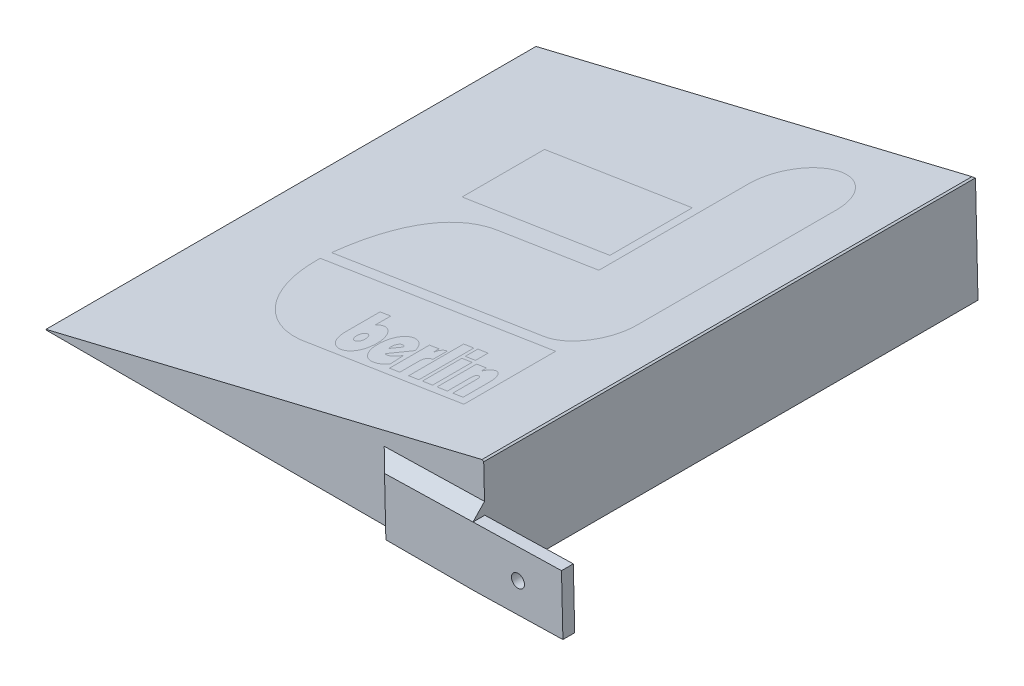
SolidWorks part; units mm, degrees
note: The reader was unsure of these and kept them because the rebuilt part matched: shared geometry of "Sketch14<4>".
ref_plane "Front Plane" through (0, 0, 0) normal (0, 0, 1) x (1, 0, 0)
ref_plane "Top Plane" through (0, 0, 0) normal (0, 1, 0) x (1, 0, 0)
ref_plane "Right Plane" through (0, 0, 0) normal (1, 0, 0) x (0, 0, -1)
sketch "Sketch1" plane through (0, 0, 0) normal (0, 0, 1) x (1, 0, 0)
  line L0 (0, 0) -> (-499.8557, 0) construction
  line L1 (0, 0) -> (50, 0)
  line L2 (0, 0) -> (0, 48)
  line L3 (0, 48) -> (50, 48)
  line L4 (50, 0) -> (50, 48)
  line L5 (-499.8557, 0) -> (-500.7205, 35.9896)
  line L6 (-500.7205, 35.9896) -> (-0.8647, 48)
  line L7 (-499.8557, 0) -> (0, 12.0104)
  line L8 (0, 12.0104) -> (-0.8647, 48)
  line L9 (-500.3361, 19.9942) -> (-0.4804, 32.0046)
  line L10 (0, 32) -> (50, 32)
  line L11 (0, 12) -> (50, 12)
  point P13 (0, 0)
  point P14 (0, 0)
  dimension "D1" = 48
  dimension "D2" = 50
  dimension "D3" = 36
  dimension "D4" = 500
  dimension "D5" = 20
  dimension "D6" = 32
  dimension "D7" = 12
sketch "Sketch2" plane through (0, 0, 0) normal (0, 0, 1) x (1, 0, 0)
  line L0 (0, 12) -> (-40, 11.0493)
  line L1 (-499.8557, 0) -> (0, 12.0104) construction
  line L2 (-40, 11.0493) -> (-40, 0)
  line L3 (0, 0) -> (-499.8557, 0) construction
  line L4 (-40, 0) -> (0, 0)
  line L5 (0, 0) -> (0, 12)
  dimension "D1" = 40
sketch "Sketch3" plane through (0, 0, 0) normal (0, 0, 1) x (1, 0, 0)
  line L0 (-39.9885, 11.0496) -> (-40.4689, 31.0438)
  line L1 (-499.8557, 0) -> (0, 12.0104) construction
  line L2 (-500.3361, 19.9942) -> (-0.4804, 32.0046) construction
  line L3 (-40.4689, 31.0438) -> (-0.4804, 32.0046)
  line L4 (-0.4804, 32.0046) -> (39.5196, 32)
  line L5 (0, 32) -> (50, 32) construction
  line L7 (0, 12) -> (50, 12) construction
  line L8 (39.5196, 12) -> (0, 12)
  line L9 (0, 12) -> (-39.9885, 11.0496)
  line L10 (-40.2287, 21.0467) -> (-0.2402, 22.0075) construction
  line L11 (0, 12.0104) -> (-0.8647, 48) construction
  line L12 (39.5196, 32) -> (39.5196, 12)
  line L13 (39.5196, 22) -> (0, 22) construction
  line L14 (0, 0) -> (0, 48) construction
  circle A0 centre (19.7598, 22) radius 2.2
  circle A1 centre (-20.2344, 21.5271) radius 2.2
  dimension "D3" = 4.4
  dimension "D1" = 40
  dimension "D2" = 40
sketch "Sketch4" plane through (0, 0, 0) normal (0, 0, 1) x (1, 0, 0)
  line L0 (-499.8558, 0) -> (-769.6838, 0) construction
  line L1 (-500.7205, 35.9896) -> (-649.8557, 0)
  line L2 (-649.8557, 0) -> (-499.8557, 0)
  line L3 (-499.8557, 0) -> (-500.7205, 35.9896)
  point P2 (-504.4259, 33.421)
  dimension "D1" = 150
extrude "Boss-Extrude1" add sketch "Sketch4" against normal blind 166.6667
ref_plane "Plane1" through (0, 0, -3) normal (0, 0, 1) x (1, 0, 0)
sketch "Sketch6" plane through (0, 0, -3) normal (0, 0, 1) x (1, 0, 0)
  line L0 (-504.8572, 0) -> (-505.5702, 29.6757)
  line L1 (-649.8557, 0) -> (-499.8557, 0) construction
  line L2 (-505.5702, 29.6757) -> (-585.109, 10.4813)
  line L3 (-585.109, 10.4813) -> (-584.8572, 0)
  line L4 (-584.8572, 0) -> (-504.8572, 0)
  line L5 (-499.8557, 0) -> (-500.7205, 35.9896) construction
  line L6 (-500.7205, 35.9896) -> (-649.8557, 0) construction
  point P8 (-585.8895, 4.3637)
  dimension "D1" = 5
  dimension "D2" = 5
  dimension "D3" = 80
extrude "Cut-Extrude1" cut sketch "Sketch6" against normal offset from surface (160.6667 mm away) 3 up to face at (-550.144, 11.9965, -166.6667)
sketch "Sketch7" plane through (-499.5673, -12.0035, 0) normal (0.9997, 0.024, 0) x (0, 0, -1)
  line L0 (20, 48.0069) -> (20, 12.0069) construction
  line L1 (166.6667, 48.0069) -> (0, 48.0069) construction
  line L2 (166.6667, 12.0069) -> (0, 12.0069) construction
  line L3 (0, 12.0069) -> (0, 48.0069) construction
  line L4 (20, 48.0069) -> (0, 12.0069) construction
  circle A0 centre (10, 30.0069) radius 2.75
  dimension "D2" = 5.5
  dimension "D1" = 20
extrude "Cut-Extrude2" [suppressed] cut sketch "Sketch7" against normal up to surface (5 mm away)
sketch "Sketch8" plane through (0, 0, 0) normal (0, 0, 1) x (1, 0, 0)
  line L0 (-500.3361, 19.9942) -> (-470.3448, 20.7149)
  line L1 (-500.3361, 19.9942) -> (-0.4804, 32.0046) construction
  line L2 (-470.3448, 20.7149) -> (-469.8644, 0.7206)
  line L3 (-499.8557, 0) -> (0, 12.0104) construction
  line L4 (-469.8644, 0.7206) -> (-499.8557, 0)
  line L5 (-499.8557, 0) -> (-529.8644, 0)
  line L6 (-649.8557, 0) -> (-499.8557, 0) construction
  line L7 (-529.8644, 0) -> (-530.3275, 19.2736)
  line L9 (-499.8557, 0) -> (-500.7205, 35.9896) construction
  line L10 (-500.3361, 19.9942) -> (-530.3275, 19.2736)
  point P15 (-510.374, 21.4504)
  dimension "D1" = 30
  dimension "D2" = 30
extrude "Boss-Extrude2" add sketch "Sketch8" along normal blind 4
sketch "Sketch9" plane through (0, 0, 4) normal (0, 0, 1) x (1, 0, 0)
  line L0 (-500.3361, 19.9942) -> (-469.8644, 0.7206) construction
  circle A0 centre (-485.1003, 10.3574) radius 2.2
  point P6 (-500.5629, 16.3746)
  dimension "D1" = 4.4
extrude "Cut-Extrude3" cut sketch "Sketch9" against normal through all
sketch "Sketch10" plane through (0, 0, -166.6667) normal (0, 0, -1) x (-1, 0, 0)
  line L0 (527.1478, 12) -> (513.1478, 12) construction
  line L2 (649.8557, 0) -> (499.8557, 0) construction
  line L3 (499.8557, 0) -> (500.7205, 35.9896) construction
  circle A0 centre (513.1478, 12) radius 2.2
  circle A1 centre (527.1478, 12) radius 2.2
  point P4 (524.0125, 6.3666)
  dimension "D1" = 4.4
  dimension "D2" = 12
  dimension "D3" = 14
  dimension "D4" = 13
extrude "Cut-Extrude4" cut sketch "Sketch10" against normal up to surface (3 mm away) up to face at (-545.0984, 10.0393, -163.6667)
chamfer "Chamfer3" distance 0.6 angle 45 3 edges at (-649.8557, 0, -83.3333) (-500.7205, 35.9896, -83.3333) (-575.2881, 17.9948, -166.6667)
chamfer "Chamfer4" distance 1 angle 45 1 edges at (-649.8557, 0, -83.0333)
sketch "Sketch14" plane through (-35.7625, 148.1942, 0) normal (-0.2346, 0.9721, 0) x (0.9721, 0.2346, 0)
  line L0 (-536.5022, 24.6662) -> (-532.5391, 24.2846)
  line L1 (-532.5391, 24.2846) -> (-532.5391, 30.6936)
  line L2 (-530.0307, 33.034) -> (-530.0115, 37.9765)
  line L3 (-532.7432, 35.7033) -> (-532.784, 35.7057)
  line L4 (-532.784, 35.7057) -> (-532.784, 37.8757)
  line L5 (-532.784, 37.8757) -> (-536.5022, 38.1901)
  line L6 (-536.5022, 38.1901) -> (-536.5022, 24.6662)
  line L7 (-525.1531, 23.574) -> (-525.1531, 42.1916)
  line L8 (-525.1531, 42.1916) -> (-529.0849, 42.5733)
  line L9 (-529.0849, 42.5733) -> (-529.0849, 23.9533)
  line L10 (-529.0849, 23.9533) -> (-525.1531, 23.574)
  line L11 (-519.8482, 37.6116) -> (-519.8482, 41.8579)
  line L12 (-519.8482, 41.8579) -> (-523.8088, 42.2636)
  line L13 (-523.8088, 42.2636) -> (-523.8088, 38.0125)
  line L14 (-523.8088, 38.0125) -> (-519.8482, 37.6116)
  line L15 (-519.8482, 23.0604) -> (-519.8482, 36.4594)
  line L16 (-519.8482, 36.4594) -> (-523.8088, 36.8603)
  line L17 (-523.8088, 36.8603) -> (-523.8088, 23.4636)
  line L18 (-523.8088, 23.4636) -> (-519.8482, 23.0604)
  line L19 (-561.0824, 45.3337) -> (-561.0824, 33.891)
  line L20 (-556.9681, 39.6832) -> (-556.9681, 45.0001)
  line L21 (-556.9681, 45.0001) -> (-561.0824, 45.3337)
  line L22 (-543.2761, 29.7839) -> (-537.5896, 34.4335)
  line L23 (-538.0097, 26.3753) -> (-538.3289, 31.3418)
  line L24 (-518.1271, 36.3346) -> (-518.1271, 22.9163)
  line L25 (-518.1271, 22.9163) -> (-514.0968, 22.5011)
  line L26 (-514.0968, 22.5011) -> (-514.0968, 30.4152)
  line L27 (-512.0228, 30.6576) -> (-512.0228, 22.309)
  line L28 (-512.0228, 22.309) -> (-508.0214, 21.925)
  line L29 (-508.0214, 21.925) -> (-508.0214, 30.7849)
  line L30 (-514.1808, 34.1694) -> (-514.2624, 34.1766)
  line L31 (-514.2624, 34.1766) -> (-514.2624, 35.9433)
  line L32 (-514.2624, 35.9433) -> (-518.1271, 36.3346)
  line L33 (-505.0617, 50.3938) -> (-505.0617, 19.3013)
  line L34 (-505.0617, 19.3013) -> (-564.875, 25.0623)
  line L35 (-596.1427, 57.6958) -> (-596.1331, 59.1673)
  line L36 (-596.1331, 59.1673) -> (-505.0617, 50.3938)
  line L37 (-541.7063, 34.4767) -> (-544.5484, 32.1579)
  line L38 (-513.7103, 54.7865) -> (-595.8307, 62.6815)
  line L39 (-566.6225, 90.4998) -> (-566.5865, 90.5094)
  line L40 (-566.5865, 90.5094) -> (-527.371, 86.736)
  line L41 (-527.371, 86.736) -> (-527.371, 137.6462)
  line L42 (-496.7851, 137.6462) -> (-496.7851, 69.9547)
  line L43 (-530.758, 121.6955) -> (-530.758, 93.7667)
  line L44 (-530.758, 93.7667) -> (-587.9501, 99.2757)
  line L45 (-587.9501, 99.2757) -> (-587.9501, 127.2044)
  line L46 (-587.9501, 127.2044) -> (-530.758, 121.6955)
  spline S0 degree 3 poles (-532.5391, 30.6936) (-532.5391, 32.4844) (-531.6846, 33.2213) (-530.6644, 33.1205) knots 0 0 0 0 1 1 1 1
  spline S1 degree 3 poles (-530.6644, 33.1205) (-530.3572, 33.0917) (-530.1939, 33.0773) (-530.0307, 33.034) knots 0 0 0 0 1 1 1 1
  spline S2 degree 3 poles (-530.0115, 37.9765) (-531.4997, 38.1181) (-532.4383, 37.338) (-532.7432, 35.7033) knots 0 0 0 0 1 1 1 1
  spline S3 degree 3 poles (-561.0824, 33.891) (-561.0824, 29.515) (-558.5835, 26.6442) (-555.0573, 26.3201) knots 0 0 0 0 1 1 1 1
  spline S4 degree 3 poles (-555.0573, 26.3201) (-552.0256, 26.0393) (-549.2652, 28.3196) (-549.2652, 32.926) knots 0 0 0 0 1 1 1 1
  spline S5 degree 3 poles (-549.2652, 32.926) (-549.2652, 36.3586) (-551.4519, 40.0144) (-554.4884, 40.2977) knots 0 0 0 0 1 1 1 1
  spline S6 degree 3 poles (-554.4884, 40.2977) (-555.6334, 40.4033) (-556.1831, 40.1224) (-556.9681, 39.6832) knots 0 0 0 0 1 1 1 1
  spline S7 degree 3 poles (-538.3289, 31.3418) (-539.1618, 30.1031) (-540.9405, 29.3374) (-542.0855, 29.4454) knots 0 0 0 0 1 1 1 1
  spline S8 degree 3 poles (-542.0855, 29.4454) (-542.4696, 29.4814) (-542.9785, 29.5799) (-543.2761, 29.7839) knots 0 0 0 0 1 1 1 1
  spline S9 degree 3 poles (-537.5896, 34.4335) (-538.4993, 37.1051) (-540.4341, 38.9727) (-542.9593, 39.2055) knots 0 0 0 0 1 1 1 1
  spline S10 degree 3 poles (-542.9593, 39.2055) (-546.099, 39.4983) (-548.6891, 37.0211) (-548.6891, 32.4387) knots 0 0 0 0 1 1 1 1
  spline S11 degree 3 poles (-548.6891, 32.4387) (-548.6891, 28.7493) (-546.2503, 25.48) (-542.8105, 25.1583) knots 0 0 0 0 1 1 1 1
  spline S12 degree 3 poles (-542.8105, 25.1583) (-540.7293, 24.9663) (-539.7283, 25.3311) (-538.0097, 26.3753) knots 0 0 0 0 1 1 1 1
  spline S13 degree 3 poles (-514.0968, 30.4152) (-514.0968, 31.0321) (-513.9024, 32.0451) (-513.079, 32.0451) knots 0 0 0 0 1 1 1 1
  spline S14 degree 3 poles (-513.079, 32.0451) (-512.2461, 32.0451) (-512.0228, 31.1953) (-512.0228, 30.6576) knots 0 0 0 0 1 1 1 1
  spline S15 degree 3 poles (-508.0214, 30.7849) (-508.0214, 33.3701) (-509.0055, 35.7633) (-511.1035, 35.9553) knots 0 0 0 0 1 1 1 1
  spline S16 degree 3 poles (-511.1035, 35.9553) (-512.1213, 36.0466) (-513.3527, 35.4513) (-514.1808, 34.1694) knots 0 0 0 0 1 1 1 1
  spline S17 degree 3 poles (-564.875, 25.0623) (-582.266, 25.7896) (-596.1427, 40.1224) (-596.1427, 57.6958) knots 0 0 0 0 1 1 1 1
  spline S18 degree 3 poles (-556.9681, 33.5141) (-556.9681, 34.6375) (-556.3128, 35.5521) (-555.3142, 35.4585) knots 0 0 0 0 1 1 1 1
  spline S19 degree 3 poles (-555.3142, 35.4585) (-554.3396, 35.3696) (-553.6795, 34.3351) (-553.6795, 33.2069) knots 0 0 0 0 1 1 1 1
  spline S20 degree 3 poles (-553.6795, 33.2069) (-553.6795, 32.0811) (-554.3396, 31.1689) (-555.3142, 31.2601) knots 0 0 0 0 1 1 1 1
  spline S21 degree 3 poles (-555.3142, 31.2601) (-556.3128, 31.3514) (-556.9681, 32.3835) (-556.9681, 33.5141) knots 0 0 0 0 1 1 1 1
  spline S22 degree 3 poles (-544.5484, 32.1579) (-544.6348, 32.3955) (-544.7212, 32.5564) (-544.7212, 33.1205) knots 0 0 0 0 1 1 1 1
  spline S23 degree 3 poles (-544.7212, 33.1205) (-544.7212, 34.2727) (-544.0203, 35.3576) (-543.0025, 35.264) knots 0 0 0 0 1 1 1 1
  spline S24 degree 3 poles (-543.0025, 35.264) (-542.4696, 35.2136) (-542.0447, 35.048) (-541.7063, 34.4767) knots 0 0 0 0 1 1 1 1
  spline S25 degree 3 poles (-595.8307, 62.6815) (-592.7581, 80.2525) (-583.6486, 92.0889) (-566.6225, 90.4998) knots 0 0 0 0 1 1 1 1
  spline S26 degree 3 poles (-527.371, 137.6462) (-527.3086, 146.0356) (-520.4867, 152.8192) (-512.0805, 152.8192) knots 0 0 0 0 1 1 1 1
  spline S27 degree 3 poles (-512.0805, 152.8192) (-503.6766, 152.8192) (-496.8547, 146.0356) (-496.7851, 137.6462) knots 0 0 0 0 1 1 1 1
  spline S28 degree 3 poles (-496.7851, 69.9547) (-496.8091, 61.5245) (-503.6454, 54.7001) (-512.0805, 54.7001) knots 0 0 0 0 1 1 1 1
  spline S29 degree 3 poles (-512.0805, 54.7001) (-512.6301, 54.7001) (-513.175, 54.7313) (-513.7103, 54.7865) knots 0 0 0 0 1 1 1 1
extrude "Cut-Extrude5" cut sketch "Sketch14" against normal blind 0.6 contours L46 L45 L44 L43 | S29 S28 L42 S27 S26 L41 L40 L39 S25 L38 | S17 L34 L33 L36 L35 S16 S15 L29 L28 L27 S14 S13 L26 L25 L24 L32 L31 L30 S12 S11 S10 S9 L22 S8 S7 L23 S6 S5 S4 S3 L19 L21 L20 S2 L2 S1 S0 L1 L0 L6 L5 L4 L3 L18 L17 L16 | S21 S20 S19 S18 | S24 S23 S22 L37
extrude "Boss-Extrude4" add sketch "Sketch14<4>" against normal up to surface (0.6 mm away) separate body contours L46 L45 L44 L43 | S29 S28 L42 S27 S26 L41 L40 L39 S25 L38 | S17 L34 L33 L36 L35 S16 S15 L29 L28 L27 S14 S13 L26 L25 L24 L32 L31 L30 S12 S11 S10 S9 L22 S8 S7 L23 S6 S5 S4 S3 L19 L21 L20 S2 L2 S1 S0 L1 L0 L6 L5 L4 L3 L18 L17 L16 | S24 S23 S22 L37 | S21 S20 S19 S18
sketch "Sketch14<4>" plane through (-35.7625, 148.1942, 0) normal (-0.2346, 0.9721, 0) x (0.9721, 0.2346, 0) same geometry as "Sketch14"
chamfer "Chamfer8" distance 4 angle 45 1 edges at (-515.3318, 19.6339, 0)
chamfer "Chamfer9" distance 4 angle 45 1 edges at (-530.144, 11.6362, 0)
